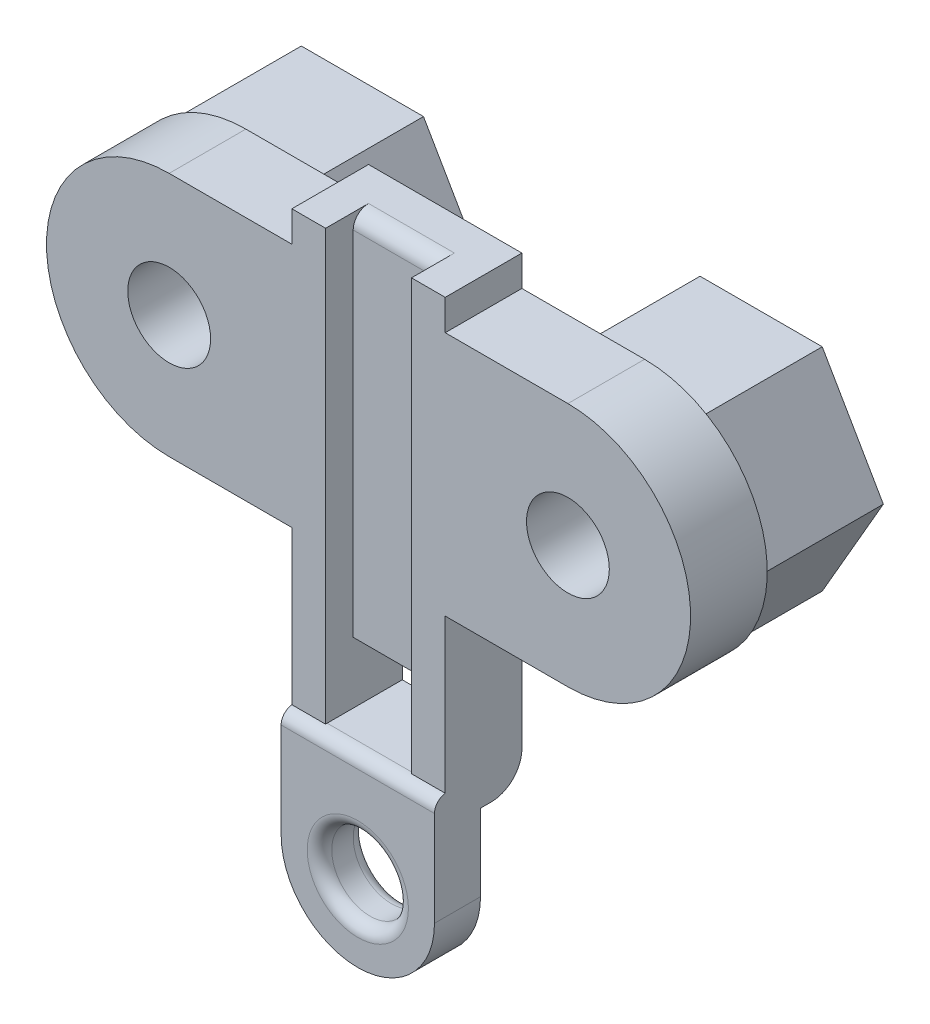
SolidWorks part; units mm, degrees
ref_plane "前视基准面" through (0, 0, 0) normal (0, 0, 1) x (1, 0, 0)
ref_plane "上视基准面" through (0, 0, 0) normal (0, 1, 0) x (1, 0, 0)
ref_plane "右视基准面" through (0, 0, 0) normal (1, 0, 0) x (0, 0, -1)
sketch "草图1" plane through (0, 0, 0) normal (0, 0, 1) x (1, 0, 0)
  line L1 (-2.5, 5) -> (2.5, 5)
  line L2 (-2.5, 5) -> (-2.5, -5)
  line L3 (-2.5, -5) -> (2.5, -5)
  line L4 (2.5, 5) -> (2.5, -5)
  line L5 (-2.5, 5) -> (2.5, -5) construction
  line L6 (-2.5, -5) -> (2.5, 5) construction
  point P0 (0, 0)
  dimension "D1" = 5
  dimension "D2" = 10
extrude "主体" add sketch "草图1" along normal blind 2.5
ref_plane "基准面4" through (0, 0, 0) normal (0, 1, 0) x (1, 0, 0)
sketch "草图2" plane through (2.5, 0, 0) normal (1, 0, 0) x (0, 0, -1)
  line L5 (1.1, 0) -> (-1.1, 0) construction
  line L6 (-2.5, 4) -> (0, 4)
  line L7 (-2.5, 4) -> (-2.5, -4)
  line L8 (-2.5, -4) -> (0, -4)
  line L9 (0, 4) -> (0, -4)
  line L10 (-2.5, 4) -> (0, -4) construction
  line L11 (-2.5, -4) -> (0, 4) construction
  line L13 (-2.5, -5) -> (-2.5, 5) construction
  line L14 (0, -5) -> (0, 5) construction
  point P0 (-1.25, 0)
  dimension "D1" = 8
extrude "凸台-拉伸2" add sketch "草图2" along normal blind 8
ref_plane "基准面5" through (6.5, 0, 0) normal (1, 0, 0) x (0, 0, -1)
hole_wizard "M2.5 间隙孔2" positions "草图9" profile "草图10" hole size "M2.5" standard "ISO" end condition up to next
sketch "草图9" plane through (0, 0, 2.5) normal (0, 0, 1) x (1, 0, 0)
  line L0 (6.5, -0.55) -> (6.5, 0.55) construction
  line L1 (1.1, 0) -> (-1.1, 0) construction
  point P0 (6.5, 0)
sketch "草图10" plane through (6.5, 0, 2.5) normal (1, 0, 0) x (0, -1, 0)
  line L0 (0, 0) -> (0, 2.5)
  line L1 (0, 2.5) -> (1.35, 2.5)
  line L2 (1.35, 2.5) -> (1.35, 0)
  line L5 (1.35, 0) -> (0, 0)
  line L11 (0, -6.35) -> (0, 107.95) construction
  dimension "通孔孔直径" = 2.7
  dimension "通孔孔深度" = 2.5
sketch "草图11" plane through (0, 0, 0) normal (0, 0, -1) x (-1, 0, 0)
  line L1 (-4.97, 2.65) -> (-8.03, 2.65)
  line L2 (-8.03, 2.65) -> (-9.56, 0)
  line L3 (-9.56, 0) -> (-8.03, -2.65)
  line L4 (-8.03, -2.65) -> (-4.97, -2.65)
  line L5 (-4.97, -2.65) -> (-3.44, 0)
  line L6 (-3.44, 0) -> (-4.97, 2.65)
  circle A0 centre (-6.5, 0) radius 2.65 construction
  point P1 (-3.44, 0)
  dimension "D1" = 5.3
extrude "拉伸-薄壁1" add sketch "草图11" along normal blind 3.8 thin thin type one direction wall 0.8
fillet "圆角1" 2 edges at (10.5, 4, 1.25) (10.5, -4, 1.25) type full round first side face at (6.5, 4, 1.25) second side face at (6.5, -4, 1.25) middle face at (10.5, 0, 1.25)
mirror "镜向1" about plane through (0, 0, 0) normal (1, 0, 0) of "圆角1", "拉伸-薄壁1", "M2.5 间隙孔2", "凸台-拉伸2"
sketch "草图13" plane through (0, -5, 0) normal (0, -1, 0) x (1, 0, 0)
  line L1 (2.5, 2.5) -> (-2.5, 2.5)
  line L2 (2.5, 2.5) -> (2.5, 0)
  line L3 (2.5, 0) -> (-2.5, 0)
  line L4 (-2.5, 2.5) -> (-2.5, 0)
extrude "凸台-拉伸3" add sketch "草图13" along normal blind 5
sketch "草图15" plane through (0, 0, 2.5) normal (0, 0, 1) x (1, 0, 0)
  line L0 (0, -1.375) -> (0, 1.375) construction
  line L1 (-1.4, 5) -> (1.4, 5)
  line L2 (-1.4, 5) -> (-1.4, -9)
  line L3 (-1.4, -9) -> (1.4, -9)
  line L4 (1.4, 5) -> (1.4, -9)
  line L5 (-1.4, 5) -> (1.4, -9) construction
  line L6 (-1.4, -9) -> (1.4, 5) construction
  line L7 (2.5, 5) -> (-2.5, 5) construction
  point P0 (0, -2)
  dimension "D1" = 14
  dimension "D2" = 2.8
extrude "导线槽" cut sketch "草图15" against normal blind 0.9
fillet "圆角2" radius 0.5 1 edges at (0, 5, 1.6)
ref_plane "导线面" through (0, 0, 2.1) normal (0, 0, 1) x (1, 0, 0)
sketch "草图16" plane through (0, 0, 2.5) normal (0, 0, 1) x (1, 0, 0)
  line L0 (2.5, -10) -> (2.5, -4) construction
  line L1 (-2.5, -10) -> (2.5, -10)
  line L2 (-2.5, -10) -> (-2.5, -9)
  line L3 (-2.5, -9) -> (2.5, -9)
  line L4 (2.5, -10) -> (2.5, -9)
  line L5 (-1.4, -9) -> (1.4, -9) construction
extrude "凸台-拉伸4" add sketch "草图16" along normal offset from surface (0.35 mm away) 0.75 up to plane "导线面"
sketch "草图17" plane through (0, -10, 0) normal (0, -1, 0) x (1, 0, 0)
  line L0 (1.54, 2.1) -> (-1.54, 2.1) construction
  line L1 (2.5, 1.35) -> (-2.5, 1.35)
  line L2 (2.5, 1.35) -> (2.5, 2.85)
  line L3 (2.5, 2.85) -> (-2.5, 2.85)
  line L4 (-2.5, 1.35) -> (-2.5, 2.85)
  line L5 (2.5, 1.35) -> (-2.5, 2.85) construction
  line L6 (2.5, 2.85) -> (-2.5, 1.35) construction
  line L7 (0, -1.375) -> (0, 1.375) construction
  point P0 (0, 2.1)
  dimension "D1" = 5
  dimension "D2" = 1.5
extrude "凸台-拉伸5" add sketch "草图17" along normal blind 5
ref_plane "基准面7" through (0, -12.5, 0) normal (0, -1, 0) x (-1, 0, 0)
sketch "草图18" plane through (0, 0, 1.35) normal (0, 0, -1) x (-1, 0, 0)
  line L0 (0, 1.375) -> (0, -1.375) construction
  line L1 (-2.31, -12.5) -> (2.31, -12.5) construction
  circle A0 centre (0, -12.5) radius 1.25
  dimension "D1" = 2.5
extrude "切除-拉伸1" cut sketch "草图18" against normal up to next
fillet "圆角3" 2 edges at (-2.5, -15, 2.1) (2.5, -15, 2.1) type full round first side face at (-2.5, -9.5, 1.675) second side face at (2.5, -9.5, 1.675) middle face at (0, -15, 2.1)
fillet "圆角4" radius 0.4 3 edges at (1.25, -12.5, 2.85) (-1.25, -12.5, 1.35) (0, -9, 2.85)
fillet "圆角5" radius 1 1 edges at (0, -10, 0)
sketch "草图19" plane through (0, 0, 1.6) normal (0, 0, 1) x (1, 0, 0)
  line L0 (1.4, -9) -> (1.4, 4.5) construction
  line L1 (-1.4, -9) -> (1.4, -9)
  line L2 (-1.4, -9) -> (-1.4, -7)
  line L3 (-1.4, -7) -> (1.4, -7)
  line L4 (1.4, -9) -> (1.4, -7)
  dimension "D1" = 2
extrude "切除-拉伸2" cut sketch "草图19" against normal up to next
